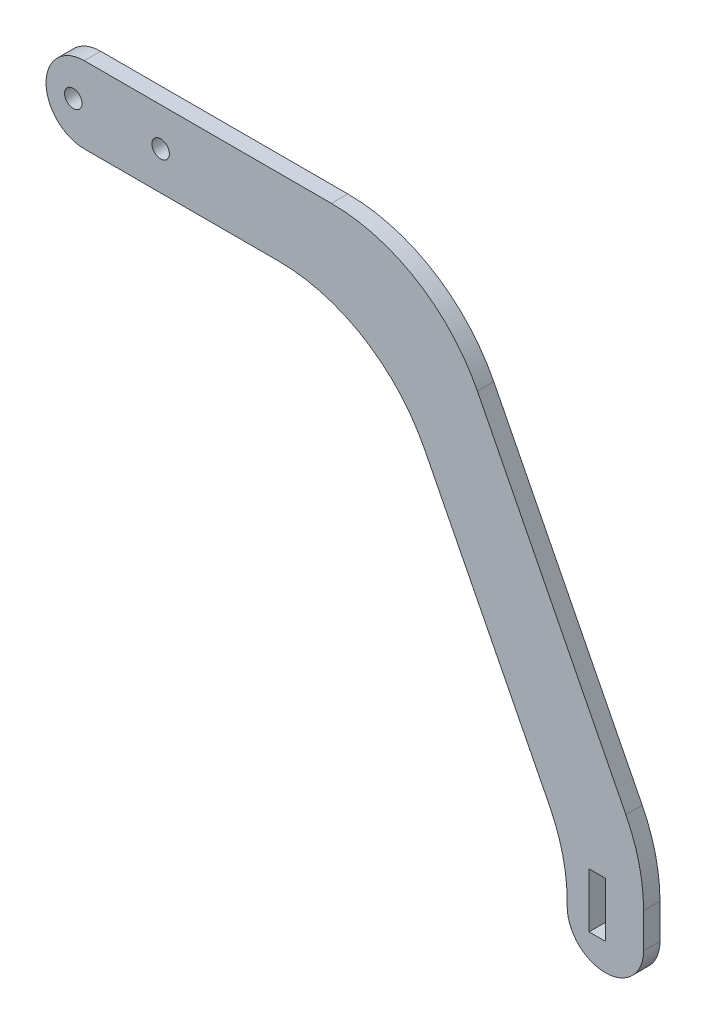
SolidWorks part; units mm, degrees
ref_plane "Plano frontal" through (0, 0, 0) normal (0, 0, 1) x (1, 0, 0)
ref_plane "Plano superior" through (0, 0, 0) normal (0, 1, 0) x (1, 0, 0)
ref_plane "Plano direito" through (0, 0, 0) normal (1, 0, 0) x (0, 0, -1)
sketch "Esboço1" plane through (0, 0, 0) normal (0, 0, 1) x (1, 0, 0)
  line L0 (0, 0) -> (0, 14)
  line L1 (0, 14) -> (70.7172, 14)
  line L2 (70.7172, 14) -> (109.5, -62.4415)
  line L3 (109.5, -62.4415) -> (109.5, -83)
  line L4 (109.5, -83) -> (95.5, -83)
  line L5 (95.5, -83) -> (95.5, -68)
  line L6 (95.5, -68) -> (61, 0)
  line L7 (61, 0) -> (0, 0)
  line L8 (5, 7) -> (21, 7) construction
  line L10 (99.5, -78) -> (102.5, -78)
  line L11 (99.5, -78) -> (99.5, -68)
  line L12 (99.5, -68) -> (102.5, -68)
  line L13 (102.5, -78) -> (102.5, -68)
  line L14 (99.5, -78) -> (102.5, -68) construction
  line L15 (99.5, -68) -> (102.5, -78) construction
  circle A0 centre (5, 7) radius 1.6
  circle A1 centre (21, 7) radius 1.6
  point P14 (34.7123, 0)
  point P15 (101, -78)
  point P16 (0, 0)
  point P17 (0, 7)
  point P18 (101, -73)
  point P23 (56.2664, 14)
  point P24 (48.2355, 0)
  dimension "D1" = 3.2
  dimension "D2" = 7
  dimension "D3" = 16
  dimension "D4" = 5
  dimension "D5" = 15
  dimension "D6" = 3
  dimension "D7" = 10
  dimension "D8" = 5
  dimension "D9" = 7
  dimension "D10" = 4
  dimension "D11" = 40
  dimension "D12" = 85
  dimension "D13" = 80
  dimension "D14" = 15
extrude "Ressalto-extrusão1" add sketch "Esboço1" along normal blind 3
fillet "Filete3" radius 30 4 edges at (95.5, -68, 1.5) (109.5, -62.4415, 1.5) (70.7172, 14, 1.5) (61, 0, 1.5)
fillet "Filete4" radius 7 4 edges at (0, 0, 1.5) (0, 14, 1.5) (109.5, -83, 1.5) (95.5, -83, 1.5)
